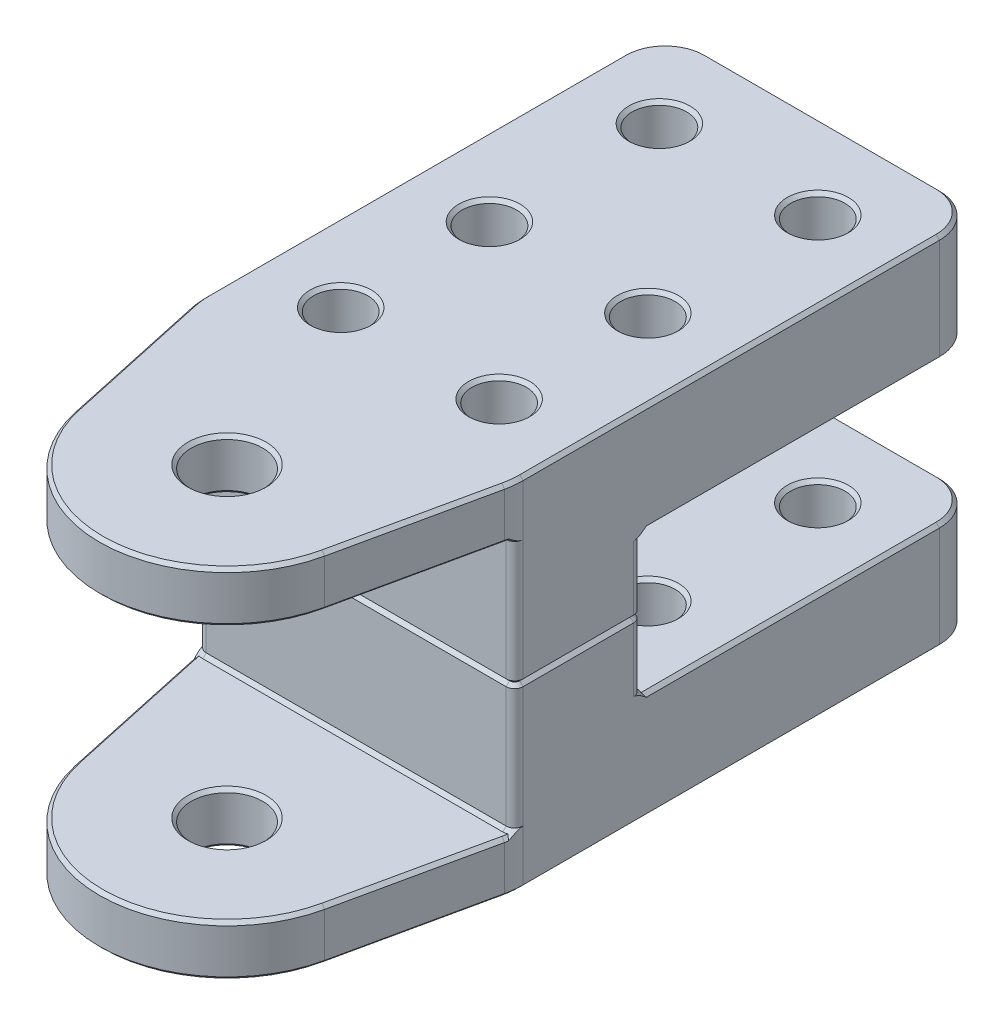
SolidWorks part; units mm, degrees
ref_plane "Front Plane" through (0, 0, 0) normal (1, 0, 0) x (0, 1, 0)
ref_plane "Top Plane" through (0, 0, 0) normal (0, 0, 1) x (0, 1, 0)
ref_plane "Right Plane" through (0, 0, 0) normal (0, 1, 0) x (-1, 0, 0)
sketch "Sketch1" plane through (0, 0, 0) normal (1, 0, 0) x (0, 1, 0)
  line L0 (-21, 45.2) -> (-15, 45.2)
  line L1 (0, 0) -> (-8.33, 0)
  line L2 (0, 0) -> (0, -40)
  line L3 (0, -40) -> (-8.33, -40)
  line L4 (-8.33, 0) -> (-8.33, -40)
  line L5 (-15, 45.2) -> (-15, 15)
  line L6 (-15, 15) -> (0, 15)
  line L7 (0, 15) -> (0, 0)
  line L8 (-21, 45.2) -> (-21, -40)
  line L9 (-21, -40) -> (-8.33, -40)
  dimension "D1" = 8.33
  dimension "D2" = 15
  dimension "D3" = 15
  dimension "D4" = 30.2
  dimension "D5" = 6
  dimension "D6" = 40
extrude "Boss-Extrude1" add sketch "Sketch1" against normal blind 18.645 contours L8 L9 L4 L1 L7 L6 L5 L0 region at (0, -13.9594, -2.3124)
sketch "Sketch2" plane through (0, -21, 0) normal (0, -1, 0) x (1, 0, 0)
  line L0 (-3.9858, 33.3791) -> (0, 15)
  line L1 (-9.3225, 15) -> (-9.3225, -40) construction
  line L4 (0, -40) -> (0, 45.2)
  line L5 (0, 45.2) -> (-18.645, 45.2)
  line L6 (-18.645, 45.2) -> (-18.645, -40)
  line L7 (-18.645, -40) -> (0, -40)
  line L8 (0, -40) -> (0, 45.2)
  line L9 (0, 45.2) -> (-18.645, 45.2)
  line L10 (-18.645, 45.2) -> (-18.645, -40)
  line L11 (-18.645, -40) -> (0, -40)
  line L12 (0, 0) -> (0, 15)
  line L13 (-18.645, 0) -> (0, 0)
  line L14 (-18.645, 15) -> (-18.645, 0)
  line L15 (0, 15) -> (-18.645, 15)
  line L16 (0, 0) -> (0, 15)
  line L17 (-18.645, 0) -> (0, 0)
  line L18 (-18.645, 15) -> (-18.645, 0)
  line L19 (0, 15) -> (-18.645, 15)
  circle A0 centre (-18.645, 30.2) radius 15
  circle A1 centre (-18.645, 30.2) radius 4.2
  circle A2 centre (-9.3225, 7.5) radius 3.2
  circle A3 centre (-9.3225, -30) radius 3.2
  circle A4 centre (-9.3225, -10) radius 3.2
  arc A5 (-0.2119, 15.9773) -> (0, 14) centre (-9.3296, 14) cw
  arc A6 (-1, 15) -> (0, 14) centre (-1, 14) cw
  line M10 (0, -40) -> (0, 45.2)
  line M11 (0, 45.2) -> (-18.645, 45.2)
  dimension "D3" = 30
  dimension "D4" = 8.4
  dimension "D10" = 6.4
  dimension "D11" = 1
  dimension "D5" = 40
  dimension "D6" = 15
  dimension "D7" = 7.5
  dimension "D8" = 10
  dimension "D9" = 10
  dimension "D1" = 0
  dimension "D2" = 0
extrude "Cut-Extrude1" cut sketch "Sketch2" against normal through all contours A0 L0 M10 M11 | L10 A1 | L1 A2 | A2 L1 | L1 A4 | A4 L1 | L1 A3 | A3 L1 | L0 A5 L19 | L19 A5 L16 region at (-3.6323, -21, 36.8228) region at (-0.0693, -21, 15.245) region at (-0.0161, -21, 14.7501) region at (-16.8625, -21, 30.2) region at (-7.9644, -21, 7.5) region at (-10.6806, -21, 7.5) region at (-7.9644, -21, -10) region at (-10.6806, -21, -10) region at (-10.6806, -21, -30) region at (-7.9644, -21, -30)
extrude "Cut-Extrude2" cut sketch "Sketch2<3>" against normal through all from surface contours L19 A6 A5 region at (-0.2422, -21, 14.779) starting at face at (-10.3618, -15, 26.7922)
sketch "Sketch2<3>" plane through (0, -21, 0) normal (0, -1, 0) x (1, 0, 0) same geometry as "Sketch2"
fillet "Fillet1" radius 1 1 edges at (0, -4.165, 0)
fillet "Fillet2" radius 5 1 edges at (0, -14.665, -40)
chamfer "Chamfer1" distance 0.4 angle 45 23 edges at (-9.3225, -21, 4.3) (-9.3225, 0, 4.3) (-9.3225, -8.33, -33.2) (-9.3225, -21, -33.2) (-9.3225, -8.33, -13.2) (-9.3225, -21, -13.2) (-14.445, -15, 30.2) (-14.445, -21, 30.2) (-9.2292, -21, 41.8766) (-2.0988, -21, 24.6782) (-11.8225, -21, -40) (-0.0531, -21, 14.9943) (-1.4645, -21, -38.5355) (0, -21, -10.5) (-0.2929, -8.33, 0.2929) (-9.8225, -8.33, 0) (-0.2929, -15, 14.7071) (-9.8225, -15, 15) (-9.8225, 0, 15) (-9.8225, 0, 0) (-0.2929, 0, 14.7071) (-0.2929, 0, 0.2929) (0, 0, 7.5)
chamfer "Chamfer2" distance 0.4 angle 45 6 edges at (-9.2292, -15, 41.8766) (-0.1227, -15, 15.5083) (-2.0988, -15, 24.6782) (-11.8225, -8.33, -40) (-1.4645, -8.33, -38.5355) (0, -8.33, -17.4899)
mirror "Mirror1" about plane through (-18.645, 0, 0) normal (1, 0, 0) of bodies 103
mirror "Mirror2" about plane through (-18.645, 0, 0) normal (0, -1, 0) of bodies 104
equation "\"D7@Sketch2\"=\"D6@Sketch2\"/2"
equation "\"D8@Sketch2\"=\"D5@Sketch2\"/4"
equation "\"D9@Sketch2\"=\"D8@Sketch2\""
